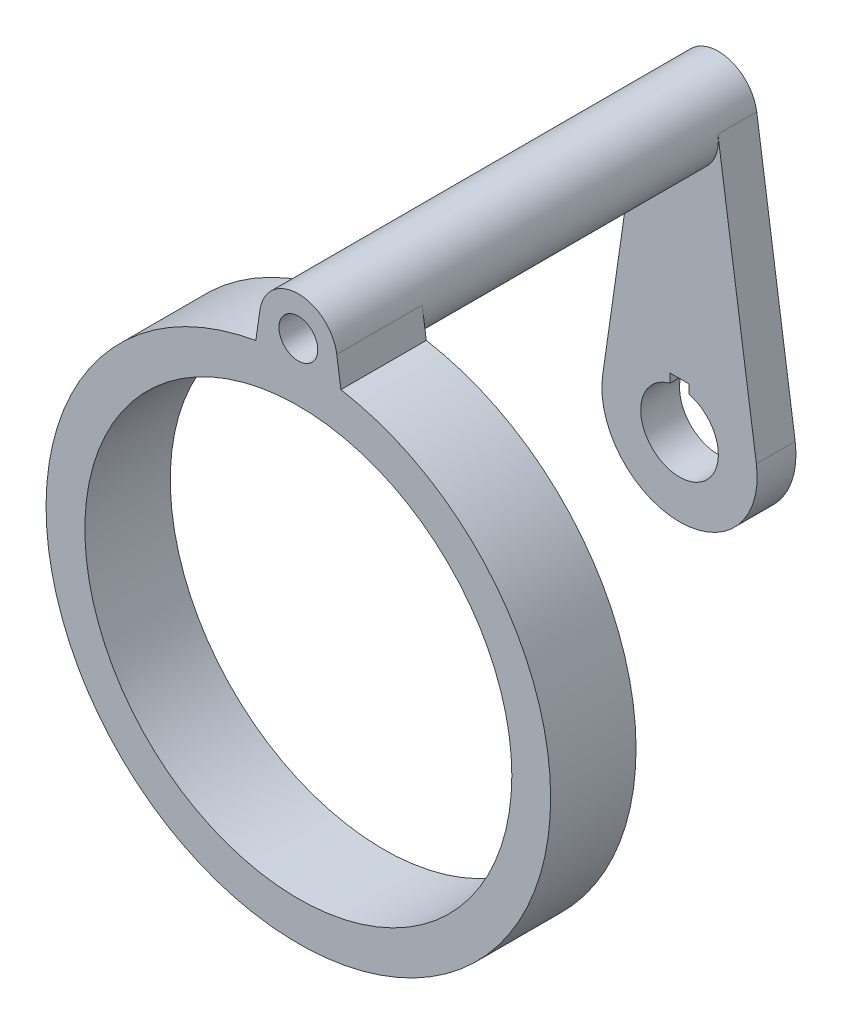
SolidWorks part; units mm, degrees
ref_plane "Front Plane" through (0, 0, 0) normal (0, 0, 1) x (1, 0, 0)
ref_plane "Top Plane" through (0, 0, 0) normal (0, 1, 0) x (1, 0, 0)
ref_plane "Right Plane" through (0, 0, 0) normal (1, 0, 0) x (0, 0, -1)
sketch "Sketch2" plane through (0, 0, 0) normal (0, 0, 1) x (1, 0, 0)
  line L0 (-19.7949, 2.8571) -> (-9.8974, 71.4286)
  line L1 (9.8974, 71.4286) -> (19.7949, 2.8571)
  line L2 (-2.5, 9.6825) -> (-2.5, 12)
  line L3 (-2.5, 12) -> (2.5, 12)
  line L4 (2.5, 12) -> (2.5, 9.6825)
  arc A0 (-19.7949, 2.8571) -> (19.7949, 2.8571) centre (0, 0) ccw
  arc A1 (-2.5, 9.6825) -> (2.5, 9.6825) centre (0, 0) ccw
  arc A2 (9.8974, 71.4286) -> (-9.8974, 71.4286) centre (0, 70) ccw
  circle A3 centre (0, 70) radius 5
  point P12 (0, 12)
  dimension "D1" = 20
  dimension "D2" = 40
  dimension "D3" = 10
  dimension "D4" = 20
  dimension "D5" = 70
  dimension "D6" = 12
  dimension "D7" = 5
extrude "Boss-Extrude1" add sketch "Sketch2" along normal blind 10
sketch "Sketch3" plane through (0, 0, 10) normal (0, 0, 1) x (1, 0, 0)
  circle A0 centre (0, 70) radius 10
  arc A1 (9.8974, 71.4286) -> (-9.8974, 71.4286) centre (0, 70) ccw construction
  circle A2 centre (0, 70) radius 5
  circle A3 centre (0, 70) radius 5 construction
extrude "Boss-Extrude2" add sketch "Sketch3" along normal blind 76.2
extrude "Boss-Extrude3" add sketch "Sketch2<2>" along normal blind 22 from surface starting at face at (10, 70, 86.2)
sketch "Sketch2<2>" plane through (0, 0, 0) normal (0, 0, 1) x (1, 0, 0) same geometry as "Sketch2"
sketch "Sketch5" plane through (0, 0, 108.2) normal (0, 0, 1) x (1, 0, 0)
  circle A0 centre (0, 0) radius 65
  dimension "D1" = 130
extrude "Boss-Extrude4" add sketch "Sketch5" against normal up to surface (22 mm away) up to face at (0, 5.9206, 86.2)
sketch "Sketch6" plane through (0, 0, 108.2) normal (0, 0, 1) x (1, 0, 0)
  circle A0 centre (0, 0) radius 55
  dimension "D1" = 110
extrude "Cut-Extrude1" cut sketch "Sketch6" against normal up to surface (22 mm away) contours A0 up to face at (0, 32.6245, 86.2)
